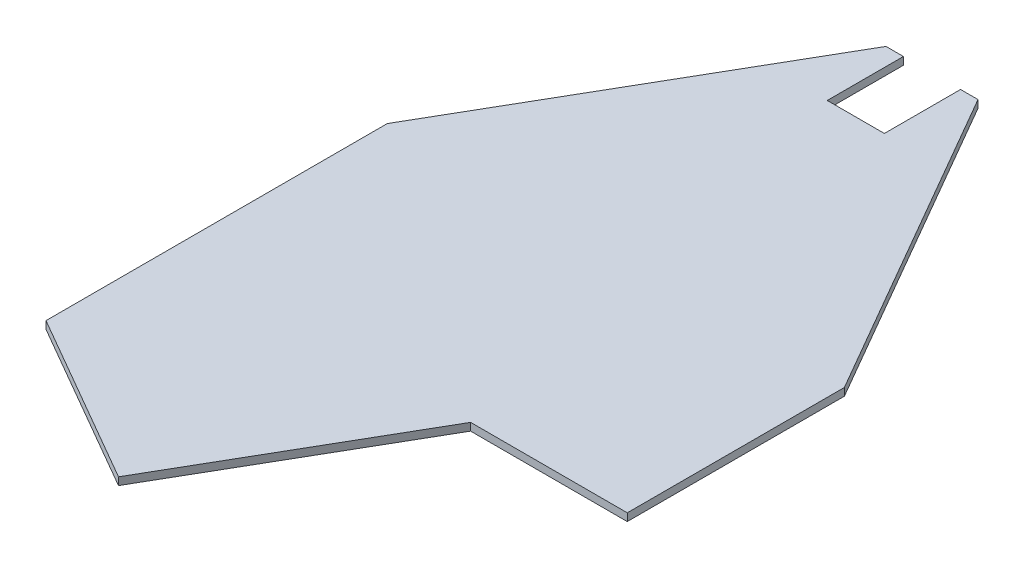
SolidWorks part; units mm, degrees
material "1.0116 (S235J2G3)"
ref_plane "Front Plane" through (0, 0, 0) normal (0, 0, 1) x (1, 0, 0)
ref_plane "Top Plane" through (0, 0, 0) normal (0, 1, 0) x (1, 0, 0)
ref_plane "Right Plane" through (0, 0, 0) normal (1, 0, 0) x (0, 0, -1)
sketch "Sketch1" plane through (0, 0, 0) normal (0, 1, 0) x (1, 0, 0)
  line L0 (0, 0) -> (0, 1800) construction
  line L1 (600, 0) -> (188.6751, 0)
  line L2 (-600, 0) -> (-600, 570)
  line L3 (-600, 570) -> (-120.7993, 1400)
  line L4 (-120.7993, 1400) -> (-75, 1400)
  line L5 (-75, 1400) -> (-75, 1200)
  line L6 (-75, 1200) -> (75, 1200)
  line L7 (75, 1400) -> (75, 1200)
  line L8 (120.7993, 1400) -> (75, 1400)
  line L9 (600, 570) -> (120.7993, 1400)
  line L10 (600, 0) -> (600, 570)
  line L13 (-149.675, -586.0397) -> (188.6751, 0)
  line L14 (-149.675, -586.0397) -> (-600, -326.0445)
  line L15 (-600, -326.0445) -> (-600, 0)
  point P3 (-97.8996, 1400)
  point P11 (0, 1200)
  dimension "D1" = 1800
  dimension "D2" = 600
  dimension "D3" = 570
  dimension "D4" = 1400
  dimension "D5" = 75
  dimension "D6" = 60
  dimension "D7" = 200
  dimension "D8" = 90
  dimension "D9" = 326.0445
  dimension "D10" = 120
  dimension "D11" = 411.3249
  dimension "D12" = 450.325
extrude "Boss-Extrude2" add sketch "Sketch1" along normal blind 20
